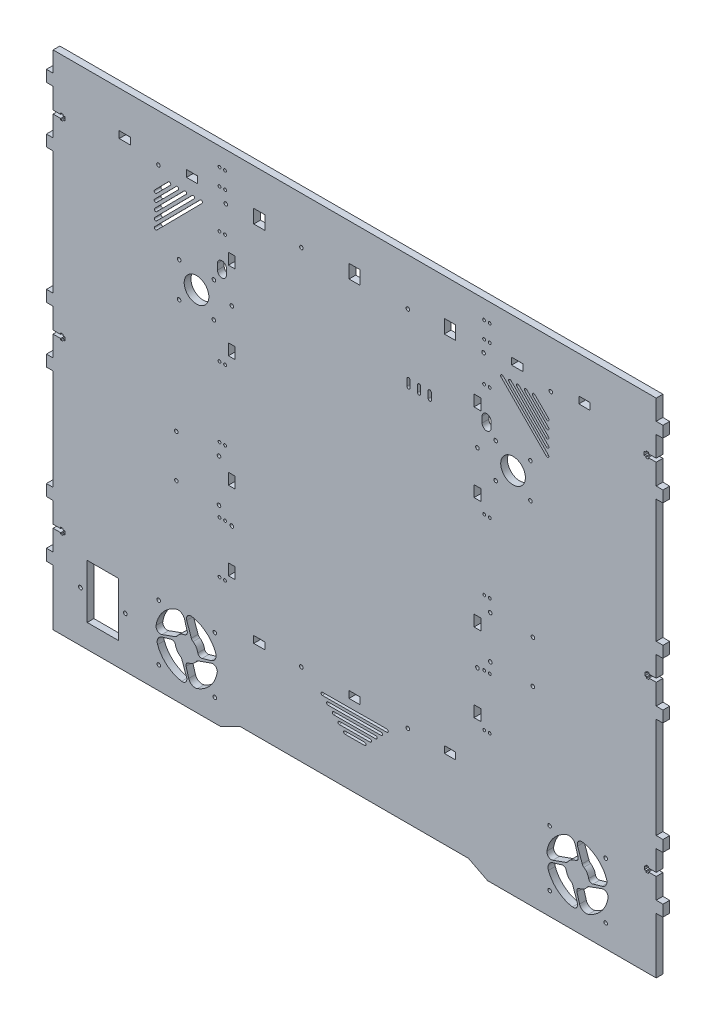
SolidWorks part; units mm, degrees
material "Клен"
ref_plane "Front" through (0, 0, 0) normal (0, 0, 1) x (1, 0, 0)
ref_plane "Top" through (0, 0, 0) normal (0, 1, 0) x (1, 0, 0)
ref_plane "Right" through (0, 0, 0) normal (1, 0, 0) x (0, 0, -1)
sketch "Эскиз1" plane through (0, 0, 0) normal (0, 0, 1) x (1, 0, 0)
  line L3 (1048.7554, 42.0072) -> (1198.2753, 42.0072)
  line L6 (1048.7554, 490.0072) -> (1586.0184, 490.0072)
  line L12 (1586.7554, 42.6812) -> (1586.7554, 42.0072)
  line L13 (1397.7554, 445.0072) -> (1407.7554, 445.0072)
  line L14 (1407.7554, 445.0072) -> (1407.7554, 457.1072)
  line L15 (1407.7554, 457.1072) -> (1397.7554, 457.1072)
  line L16 (1397.7554, 457.1072) -> (1397.7554, 445.0072)
  line L17 (1048.7554, 42.6769) -> (1048.7554, 42.0072)
  line L21 (1227.7554, 445.0072) -> (1237.7554, 445.0072)
  line L22 (1237.7554, 445.0072) -> (1237.7554, 457.1072)
  line L23 (1237.7554, 457.1072) -> (1227.7554, 457.1072)
  line L24 (1227.7554, 457.1072) -> (1227.7554, 445.0072)
  line L25 (1312.7554, 445.0072) -> (1322.7554, 445.0072)
  line L26 (1322.7554, 445.0072) -> (1322.7554, 457.1072)
  line L27 (1322.7554, 457.1072) -> (1312.7554, 457.1072)
  line L28 (1312.7554, 457.1072) -> (1312.7554, 445.0072)
  line L48 (1167.7554, 451.0072) -> (1177.7554, 451.0072)
  line L49 (1177.7554, 451.0072) -> (1177.7554, 457.1072)
  line L50 (1177.7554, 457.1072) -> (1167.7554, 457.1072)
  line L51 (1167.7554, 457.1072) -> (1167.7554, 451.0072)
  line L56 (1457.7554, 451.0072) -> (1467.7554, 451.0072)
  line L57 (1467.7554, 451.0072) -> (1467.7554, 457.1072)
  line L58 (1467.7554, 457.1072) -> (1457.7554, 457.1072)
  line L59 (1457.7554, 457.1072) -> (1457.7554, 451.0072)
  line L92 (1397.7554, 121.0049) -> (1407.7554, 121.0049)
  line L93 (1407.7554, 121.0049) -> (1407.7554, 127.1049)
  line L94 (1407.7554, 127.1049) -> (1397.7554, 127.1049)
  line L95 (1397.7554, 127.1049) -> (1397.7554, 121.0049)
  line L96 (1312.7554, 121.0049) -> (1322.7554, 121.0049)
  line L97 (1322.7554, 121.0049) -> (1322.7554, 127.1049)
  line L98 (1322.7554, 127.1049) -> (1312.7554, 127.1049)
  line L99 (1312.7554, 127.1049) -> (1312.7554, 121.0049)
  line L100 (1227.7554, 121.0049) -> (1237.7554, 121.0049)
  line L101 (1237.7554, 121.0049) -> (1237.7554, 127.1049)
  line L102 (1237.7554, 127.1049) -> (1227.7554, 127.1049)
  line L143 (1227.7554, 127.1049) -> (1227.7554, 121.0049)
  line L148 (1079.1628, 110.8776) -> (1079.1628, 62.8776)
  line L154 (1455.45, 437.0308) -> (1488.8515, 403.2582)
  line L159 (1107.1628, 110.8776) -> (1079.1628, 110.8776)
  line L160 (1079.1628, 62.8776) -> (1107.1628, 62.8776)
  line L161 (1107.1628, 62.8776) -> (1107.1628, 110.8776)
  line L172 (1326.6292, 91.6177) -> (1309.1294, 91.521)
  line L173 (1309.1156, 94.021) -> (1326.6154, 94.1176)
  line L174 (1331.6015, 96.6452) -> (1304.1019, 96.4933)
  line L175 (1304.0881, 98.9933) -> (1331.5877, 99.1452)
  line L176 (1336.5738, 101.6728) -> (1299.0744, 101.4656)
  line L177 (1299.0605, 103.9656) -> (1336.56, 104.1727)
  line L178 (1289.0054, 113.9102) -> (1346.5046, 114.2278)
  line L179 (1346.5184, 111.7279) -> (1289.0193, 111.4102)
  line L180 (1341.5461, 106.7003) -> (1294.0468, 106.4379)
  line L181 (1294.033, 108.9379) -> (1341.5323, 109.2003)
  line L182 (1490.629, 405.0162) -> (1457.2275, 438.7888)
  line L183 (1448.379, 437.0699) -> (1488.8124, 396.1873)
  line L184 (1469.5919, 436.9527) -> (1488.9296, 417.4001)
  line L185 (1476.6629, 436.9136) -> (1488.9687, 424.4711)
  line L186 (1490.5899, 397.9452) -> (1450.1565, 438.8279)
  line L187 (1490.7071, 419.1581) -> (1471.3694, 438.7107)
  line L188 (1462.521, 436.9918) -> (1488.8906, 410.3292)
  line L189 (1490.7462, 426.2291) -> (1478.4404, 438.6716)
  line L198 (1530.3174, 86.3769) -> (1538.4752, 88.7337)
  line L199 (1494.5571, 86.9094) -> (1506.2002, 91.0661)
  line L200 (1517.0418, 100.6255) -> (1514.685, 108.7833)
  line L201 (1502.7664, 87.3542) -> (1494.6086, 84.9974)
  line L202 (1538.538, 86.8062) -> (1526.8948, 82.6495)
  line L203 (1516.0532, 73.09) -> (1518.4101, 64.9322)
  line L204 (1516.4826, 64.8695) -> (1512.3258, 76.5127)
  line L205 (1516.6012, 108.8616) -> (1520.758, 97.2184)
  line L210 (1215.2753, 50.7072) -> (1198.2753, 42.0072)
  line L268 (1215.2753, 50.7072) -> (1419.2753, 50.7072)
  line L269 (1419.2753, 50.7072) -> (1436.2753, 42.0072)
  line L270 (1436.2753, 42.0072) -> (1586.7554, 42.0072)
  line L271 (1490.6681, 412.0872) -> (1464.2985, 438.7498)
  line L272 (1181.6577, 437.9061) -> (1141.2243, 397.0234)
  line L273 (1139.4468, 398.7814) -> (1179.8802, 439.6641)
  line L274 (1139.2905, 427.0652) -> (1151.5963, 439.5078)
  line L275 (1174.5867, 437.867) -> (1141.1852, 404.0944)
  line L276 (1153.3738, 437.7498) -> (1141.068, 425.3073)
  line L277 (1139.3296, 419.9943) -> (1158.6673, 439.5469)
  line L278 (1160.4448, 437.7889) -> (1141.1071, 418.2363)
  line L279 (1167.5157, 437.8279) -> (1141.1461, 411.1653)
  line L280 (1139.3686, 412.9233) -> (1165.7382, 439.5859)
  line L301 (1139.4077, 405.8524) -> (1172.8092, 439.625)
  line L302 (1527.7554, 457.1072) -> (1517.7554, 457.1072)
  line L303 (1517.7554, 451.0072) -> (1527.7554, 451.0072)
  line L304 (1517.7554, 457.1072) -> (1517.7554, 451.0072)
  line L305 (1527.7554, 451.0072) -> (1527.7554, 457.1072)
  line L306 (1117.7554, 451.0072) -> (1117.7554, 457.1072)
  line L307 (1107.7554, 457.1072) -> (1107.7554, 451.0072)
  line L308 (1117.7554, 457.1072) -> (1107.7554, 457.1072)
  line L309 (1107.7554, 451.0072) -> (1117.7554, 451.0072)
  line L310 (1167.825, 64.8695) -> (1163.6683, 76.5127)
  line L348 (1592.7554, 462.0158) -> (1586.7554, 461.9158)
  line L358 (1059.2554, 440.4572) -> (1059.2554, 443.5572)
  line L359 (1057.7554, 439.2572) -> (1057.7554, 440.4572)
  line L360 (1048.7554, 477.0072) -> (1048.7554, 490.0072)
  line L361 (1057.7554, 270.4572) -> (1059.2554, 270.4572)
  line L362 (1055.5554, 270.4572) -> (1055.5554, 269.2572)
  line L363 (1430.3554, 401.9072) -> (1430.3554, 411.9072)
  line L364 (1430.3554, 411.9072) -> (1424.2554, 411.9072)
  line L365 (1424.2554, 411.9072) -> (1424.2554, 401.9072)
  line L366 (1424.2554, 401.9072) -> (1430.3554, 401.9072)
  line L367 (1430.3554, 331.9072) -> (1430.3554, 341.9072)
  line L368 (1430.3554, 341.9072) -> (1424.2554, 341.9072)
  line L369 (1424.2554, 341.9072) -> (1424.2554, 331.9072)
  line L370 (1424.2554, 331.9072) -> (1430.3554, 331.9072)
  line L371 (1430.3554, 231.9072) -> (1430.3554, 241.9072)
  line L372 (1430.3554, 241.9072) -> (1424.2554, 241.9072)
  line L373 (1424.2554, 241.9072) -> (1424.2554, 231.9072)
  line L374 (1424.2554, 231.9072) -> (1430.3554, 231.9072)
  line L375 (1424.2554, 171.9072) -> (1424.2554, 161.9072)
  line L376 (1424.2554, 161.9072) -> (1430.3554, 161.9072)
  line L377 (1430.3554, 161.9072) -> (1430.3554, 171.9072)
  line L378 (1430.3554, 171.9072) -> (1424.2554, 171.9072)
  line L379 (1205.1554, 161.9072) -> (1211.2554, 161.9072)
  line L380 (1211.2554, 161.9072) -> (1211.2554, 171.9072)
  line L381 (1205.1554, 171.9072) -> (1205.1554, 161.9072)
  line L382 (1211.2554, 171.9072) -> (1205.1554, 171.9072)
  line L383 (1211.2554, 231.9072) -> (1211.2554, 241.9072)
  line L384 (1211.2554, 241.9072) -> (1205.1554, 241.9072)
  line L385 (1205.1554, 241.9072) -> (1205.1554, 231.9072)
  line L386 (1205.1554, 231.9072) -> (1211.2554, 231.9072)
  line L387 (1205.1554, 331.9072) -> (1211.2554, 331.9072)
  line L388 (1211.2554, 331.9072) -> (1211.2554, 341.9072)
  line L389 (1205.1554, 341.9072) -> (1205.1554, 331.9072)
  line L390 (1211.2554, 341.9072) -> (1205.1554, 341.9072)
  line L391 (1205.1554, 401.9072) -> (1211.2554, 401.9072)
  line L392 (1211.2554, 401.9072) -> (1211.2554, 411.9072)
  line L393 (1211.2554, 411.9072) -> (1205.1554, 411.9072)
  line L394 (1205.1554, 411.9072) -> (1205.1554, 401.9072)
  line L395 (1145.8995, 86.9094) -> (1157.5427, 91.0661)
  line L396 (1189.8804, 86.8062) -> (1178.2373, 82.6495)
  line L397 (1167.3957, 73.09) -> (1169.7525, 64.9322)
  line L398 (1154.1089, 87.3542) -> (1145.951, 84.9974)
  line L399 (1181.6599, 86.3769) -> (1189.8177, 88.7337)
  line L400 (1167.9437, 108.8616) -> (1172.1004, 97.2184)
  line L414 (1057.7554, 119.2572) -> (1057.7554, 120.4572)
  line L415 (1168.3843, 100.6255) -> (1166.0274, 108.7833)
  line L416 (1317.7554, 12.4246) -> (1317.7554, 537.1765) construction
  line L417 (1586.7554, 537.1765) -> (1586.7554, 12.4246) construction
  line L418 (1048.7554, 537.1765) -> (1048.7554, -11.6164) construction
  line L419 (1042.7554, 92.0072) -> (1042.7554, 102.0072)
  line L420 (1431.4302, 398.3485) -> (1431.4302, 393.0655)
  line L421 (1439.4302, 393.0655) -> (1439.4302, 398.3485)
  line L422 (1048.7554, 123.5572) -> (1048.7554, 141.9072)
  line L423 (1048.7554, 472.1072) -> (1048.7554, 477.0072)
  line L424 (1195.3774, 398.4163) -> (1195.3774, 393.1334)
  line L425 (1203.3774, 393.1334) -> (1203.3774, 398.4163)
  line L426 (1059.2554, 123.5572) -> (1057.7554, 123.5572)
  line L427 (1057.7554, 274.7572) -> (1055.5554, 274.7572)
  line L428 (1383.3554, 394.0072) -> (1383.3554, 388.0072)
  line L429 (1386.1554, 388.0072) -> (1386.1554, 394.0072)
  line L430 (1042.7554, 102.0072) -> (1048.7554, 102.1072)
  line L431 (1057.7554, 120.4572) -> (1059.2554, 120.4572)
  line L432 (1373.8554, 394.0072) -> (1373.8554, 388.0072)
  line L433 (1376.6554, 388.0072) -> (1376.6554, 394.0072)
  line L434 (1042.7554, 142.0072) -> (1042.7554, 152.0072)
  line L435 (1042.7554, 302.0072) -> (1048.7554, 302.1072)
  line L436 (1364.3554, 394.0072) -> (1364.3554, 388.0072)
  line L437 (1367.1554, 388.0072) -> (1367.1554, 394.0072)
  line L438 (1055.5554, 120.4572) -> (1055.5554, 119.2572)
  line L439 (1048.7554, 411.9072) -> (1042.7554, 412.0072)
  line L440 (1055.5554, 444.7572) -> (1055.5554, 443.5572)
  line L441 (1057.7554, 124.7572) -> (1055.5554, 124.7572)
  line L442 (1055.5554, 443.5572) -> (1048.7554, 443.5572)
  line L443 (1048.7554, 120.4572) -> (1055.5554, 120.4572)
  line L444 (1042.7554, 242.0072) -> (1042.7554, 252.0072)
  line L445 (1055.5554, 269.2572) -> (1057.7554, 269.2572)
  line L446 (1055.5554, 274.7572) -> (1055.5554, 273.5572)
  line L447 (1048.7554, 461.9072) -> (1042.7554, 462.0072)
  line L448 (1048.7554, 102.1072) -> (1048.7554, 120.4572)
  line L449 (1057.7554, 440.4572) -> (1059.2554, 440.4572)
  line L450 (1048.7554, 252.1072) -> (1048.7554, 270.4572)
  line L451 (1042.7554, 292.0072) -> (1042.7554, 302.0072)
  line L452 (1042.7554, 472.0072) -> (1048.7554, 472.1072)
  line L453 (1059.2554, 443.5572) -> (1057.7554, 443.5572)
  line L454 (1048.7554, 42.6769) -> (1048.7554, 91.9072)
  line L455 (1048.7554, 273.5572) -> (1048.7554, 291.9072)
  line L456 (1055.5554, 440.4572) -> (1055.5554, 439.2572)
  line L457 (1055.5554, 439.2572) -> (1057.7554, 439.2572)
  line L458 (1042.7554, 422.0072) -> (1048.7554, 422.1072)
  line L459 (1048.7554, 443.5572) -> (1048.7554, 461.9072)
  line L460 (1048.7554, 141.9072) -> (1042.7554, 142.0072)
  line L461 (1048.7554, 302.1072) -> (1048.7554, 411.9072)
  line L462 (1048.7554, 91.9072) -> (1042.7554, 92.0072)
  line L463 (1048.7554, 270.4572) -> (1055.5554, 270.4572)
  line L464 (1048.7554, 291.9072) -> (1042.7554, 292.0072)
  line L465 (1059.2554, 120.4572) -> (1059.2554, 123.5572)
  line L466 (1057.7554, 273.5572) -> (1057.7554, 274.7572)
  line L467 (1042.7554, 252.0072) -> (1048.7554, 252.1072)
  line L468 (1059.2554, 273.5572) -> (1057.7554, 273.5572)
  line L469 (1048.7554, 422.1072) -> (1048.7554, 440.4572)
  line L470 (1042.7554, 462.0072) -> (1042.7554, 472.0072)
  line L471 (1057.7554, 269.2572) -> (1057.7554, 270.4572)
  line L472 (1057.7554, 443.5572) -> (1057.7554, 444.7572)
  line L473 (1042.7554, 152.0072) -> (1048.7554, 152.1072)
  line L474 (1059.2554, 270.4572) -> (1059.2554, 273.5572)
  line L475 (1055.5554, 273.5572) -> (1048.7554, 273.5572)
  line L476 (1048.7554, 152.1072) -> (1048.7554, 241.9072)
  line L477 (1057.7554, 444.7572) -> (1055.5554, 444.7572)
  line L478 (1055.5554, 124.7572) -> (1055.5554, 123.5572)
  line L479 (1048.7554, 241.9072) -> (1042.7554, 242.0072)
  line L480 (1055.5554, 123.5572) -> (1048.7554, 123.5572)
  line L481 (1057.7554, 123.5572) -> (1057.7554, 124.7572)
  line L482 (1055.5554, 119.2572) -> (1057.7554, 119.2572)
  line L483 (1042.7554, 412.0072) -> (1042.7554, 422.0072)
  line L484 (1048.7554, 440.4572) -> (1055.5554, 440.4572)
  line L487 (1586.0184, 490.0072) -> (1586.7554, 490.0072)
  line L488 (1586.7554, 302.1072) -> (1592.7554, 302.0072)
  line L489 (1592.7554, 252.0072) -> (1592.7554, 242.0072)
  line L490 (1579.6985, 444.7615) -> (1577.4985, 444.7615)
  line L491 (1592.7554, 472.0072) -> (1592.7554, 462.0158)
  line L492 (1579.9554, 120.4572) -> (1586.7554, 120.4572)
  line L493 (1592.7554, 102.0072) -> (1592.7554, 92.0072)
  line L494 (1579.9554, 123.5572) -> (1579.9554, 124.7572)
  line L495 (1586.7554, 490.0072) -> (1586.7554, 472.1072)
  line L496 (1577.7554, 120.4572) -> (1577.7554, 119.2572)
  line L497 (1578.2356, 269.2572) -> (1580.4356, 269.2572)
  line L498 (1575.9985, 440.4615) -> (1577.4985, 440.4615)
  line L499 (1580.4356, 274.7572) -> (1578.2356, 274.7572)
  line L500 (1577.7554, 123.5572) -> (1576.2554, 123.5572)
  line L501 (1576.7356, 273.5572) -> (1576.7356, 270.4572)
  line L502 (1586.4985, 443.5615) -> (1586.7554, 443.5615)
  line L503 (1578.2356, 274.7572) -> (1578.2356, 273.5572)
  line L504 (1577.4985, 439.2615) -> (1579.6985, 439.2615)
  line L505 (1576.2554, 120.4572) -> (1577.7554, 120.4572)
  line L506 (1586.4985, 443.5615) -> (1579.6985, 443.5615)
  line L507 (1586.7554, 141.9072) -> (1586.7554, 123.5572)
  line L508 (1592.7554, 142.0072) -> (1586.7554, 141.9072)
  line L509 (1586.7554, 252.1072) -> (1592.7554, 252.0072)
  line L510 (1578.2356, 270.4572) -> (1578.2356, 269.2572)
  line L511 (1580.4356, 270.4572) -> (1586.7554, 270.4572)
  line L512 (1579.9554, 124.7572) -> (1577.7554, 124.7572)
  line L513 (1577.7554, 124.7572) -> (1577.7554, 123.5572)
  line L514 (1592.7554, 142.0072) -> (1592.7554, 152.0072)
  line L515 (1579.6985, 440.4615) -> (1586.4985, 440.4615)
  line L516 (1592.7554, 412.0072) -> (1586.7554, 411.9072)
  line L517 (1580.4356, 269.2572) -> (1580.4356, 270.4572)
  line L518 (1586.7554, 91.9072) -> (1586.7554, 42.6812)
  line L519 (1592.7554, 242.0072) -> (1586.7554, 241.9072)
  line L520 (1579.6985, 439.2615) -> (1579.6985, 440.4615)
  line L521 (1580.4356, 273.5572) -> (1580.4356, 274.7572)
  line L522 (1586.7554, 270.4572) -> (1586.7554, 252.1072)
  line L523 (1577.4985, 443.5615) -> (1575.9985, 443.5615)
  line L524 (1586.7554, 152.1072) -> (1592.7554, 152.0072)
  line L525 (1577.7554, 119.2572) -> (1579.9554, 119.2572)
  line L526 (1592.7554, 422.0072) -> (1592.7554, 412.0072)
  line L527 (1586.7554, 422.1072) -> (1592.7554, 422.0072)
  line L528 (1579.9554, 119.2572) -> (1579.9554, 120.4572)
  line L529 (1586.7554, 273.5572) -> (1580.4356, 273.5572)
  line L530 (1586.7554, 123.5572) -> (1579.9554, 123.5572)
  line L531 (1586.4985, 440.4615) -> (1586.7554, 440.4615)
  line L532 (1576.7356, 270.4572) -> (1578.2356, 270.4572)
  line L533 (1586.7554, 461.9158) -> (1586.7554, 443.5615)
  line L534 (1575.9985, 443.5615) -> (1575.9985, 440.4615)
  line L535 (1592.7554, 292.0072) -> (1586.7554, 291.9072)
  line L536 (1586.7554, 120.4572) -> (1586.7554, 102.1072)
  line L537 (1576.2554, 123.5572) -> (1576.2554, 120.4572)
  line L538 (1586.7554, 102.1072) -> (1592.7554, 102.0072)
  line L539 (1592.7554, 92.0072) -> (1586.7554, 91.9072)
  line L540 (1586.7554, 411.9072) -> (1586.7554, 302.1072)
  line L541 (1592.7554, 302.0072) -> (1592.7554, 292.0072)
  line L542 (1577.4985, 444.7615) -> (1577.4985, 443.5615)
  line L543 (1579.6985, 443.5615) -> (1579.6985, 444.7615)
  line L544 (1586.7554, 241.9072) -> (1586.7554, 152.1072)
  line L545 (1586.7554, 440.4615) -> (1586.7554, 422.1072)
  line L546 (1586.7554, 291.9072) -> (1586.7554, 273.5572)
  line L547 (1578.2356, 273.5572) -> (1576.7356, 273.5572)
  line L548 (1586.7554, 472.1072) -> (1592.7554, 472.0072)
  line L549 (1577.4985, 440.4615) -> (1577.4985, 439.2615)
  circle A4 centre (1202.7554, 448.0572) radius 1.6
  circle A5 centre (1432.7554, 448.0572) radius 1.6
  circle A6 centre (1365.2554, 448.0572) radius 1.6
  circle A7 centre (1270.2554, 448.0572) radius 1.6
  circle A14 centre (1365.2554, 124.0549) radius 1.6
  circle A15 centre (1270.2554, 124.0549) radius 1.6
  circle A20 centre (1492.7554, 448.0572) radius 1.6
  circle A21 centre (1142.7554, 448.0572) radius 1.6
  circle A24 centre (1073.1628, 86.8776) radius 1.65
  circle A25 centre (1113.1628, 86.8776) radius 1.65
  arc A36 (1326.6292, 91.6177) -> (1326.6154, 94.1176) centre (1326.6223, 92.8677) ccw
  arc A37 (1309.1156, 94.021) -> (1309.1294, 91.521) centre (1309.1225, 92.771) ccw
  arc A38 (1304.0881, 98.9933) -> (1304.1019, 96.4933) centre (1304.095, 97.7433) ccw
  arc A39 (1331.6015, 96.6452) -> (1331.5877, 99.1452) centre (1331.5946, 97.8952) ccw
  arc A40 (1336.5738, 101.6728) -> (1336.56, 104.1727) centre (1336.5669, 102.9228) ccw
  arc A41 (1299.0605, 103.9656) -> (1299.0744, 101.4656) centre (1299.0674, 102.7156) ccw
  arc A42 (1294.033, 108.9379) -> (1294.0468, 106.4379) centre (1294.0399, 107.6879) ccw
  arc A43 (1341.5461, 106.7003) -> (1341.5323, 109.2003) centre (1341.5392, 107.9503) ccw
  arc A44 (1346.5184, 111.7279) -> (1346.5046, 114.2278) centre (1346.5115, 112.9779) ccw
  arc A45 (1289.0054, 113.9102) -> (1289.0193, 111.4102) centre (1289.0124, 112.6602) ccw
  arc A46 (1157.5427, 91.0661) -> (1159.5017, 92.5785) centre (1156.1978, 94.8332) ccw
  arc A47 (1450.1565, 438.8279) -> (1448.379, 437.0699) centre (1449.2678, 437.9489) ccw
  arc A48 (1471.3694, 438.7107) -> (1469.5919, 436.9527) centre (1470.4807, 437.8317) ccw
  arc A49 (1457.2275, 438.7888) -> (1455.45, 437.0308) centre (1456.3388, 437.9098) ccw
  arc A50 (1488.9687, 424.4711) -> (1490.7462, 426.2291) centre (1489.8574, 425.3501) ccw
  arc A51 (1488.8515, 403.2582) -> (1490.629, 405.0162) centre (1489.7403, 404.1372) ccw
  arc A52 (1488.8124, 396.1873) -> (1490.5899, 397.9452) centre (1489.7012, 397.0662) ccw
  arc A53 (1488.8906, 410.3292) -> (1490.6681, 412.0872) centre (1489.7793, 411.2082) ccw
  arc A54 (1488.9296, 417.4001) -> (1490.7071, 419.1581) centre (1489.8184, 418.2791) ccw
  arc A55 (1478.4404, 438.6716) -> (1476.6629, 436.9136) centre (1477.5516, 437.7926) ccw
  arc A56 (1464.2985, 438.7498) -> (1462.521, 436.9918) centre (1463.4097, 437.8708) ccw
  arc A57 (1139.3296, 419.9943) -> (1141.1071, 418.2363) centre (1140.2183, 419.1153) ccw
  arc A58 (1174.5867, 437.867) -> (1172.8092, 439.625) centre (1173.698, 438.746) ccw
  arc A59 (1167.5157, 437.8279) -> (1165.7382, 439.5859) centre (1166.627, 438.7069) ccw
  arc A60 (1139.4468, 398.7814) -> (1141.2243, 397.0234) centre (1140.3355, 397.9024) ccw
  arc A61 (1153.3738, 437.7498) -> (1151.5963, 439.5078) centre (1152.4851, 438.6288) ccw
  arc A62 (1139.3686, 412.9233) -> (1141.1461, 411.1653) centre (1140.2574, 412.0443) ccw
  arc A63 (1160.4448, 437.7889) -> (1158.6673, 439.5469) centre (1159.556, 438.6679) ccw
  arc A64 (1181.6577, 437.9061) -> (1179.8802, 439.6641) centre (1180.7689, 438.7851) ccw
  arc A65 (1139.2905, 427.0652) -> (1141.068, 425.3073) centre (1140.1793, 426.1863) ccw
  arc A66 (1139.4077, 405.8524) -> (1141.1852, 404.0944) centre (1140.2965, 404.9734) ccw
  arc A67 (1166.0274, 108.7833) -> (1158.15, 112.7336) centre (1160.2632, 107.118) ccw
  arc A68 (1189.8177, 88.7337) -> (1193.7679, 96.6112) centre (1188.1523, 94.498) ccw
  circle A69 centre (1143.0318, 112.013) radius 1.6
  circle A70 centre (1143.0318, 62.013) radius 1.6
  arc A71 (1166.0477, 96.8429) -> (1168.3843, 100.6255) centre (1165.5021, 99.7929) ccw
  arc A72 (1145.951, 84.9974) -> (1142.0008, 77.1199) centre (1147.6164, 79.2331) ccw
  arc A100 (1178.2373, 82.6495) -> (1176.2782, 81.1371) centre (1179.5822, 78.8823) ccw
  arc A102 (1538.4752, 88.7337) -> (1542.4254, 96.6112) centre (1536.8099, 94.498) ccw
  arc A103 (1526.2875, 60.982) -> (1543.8306, 82.3942) centre (1516.5531, 86.85) ccw
  arc A104 (1512.3258, 76.5127) -> (1510.8135, 78.4717) centre (1508.5587, 75.1677) ccw
  arc A105 (1518.3898, 76.8727) -> (1516.0532, 73.09) centre (1518.9354, 73.9227) ccw
  arc A106 (1489.2645, 91.3213) -> (1494.5571, 86.9094) centre (1493.2122, 90.6765) ccw
  arc A107 (1512.0706, 59.5769) -> (1516.4826, 64.8695) centre (1512.7155, 63.5246) ccw
  arc A108 (1506.2002, 91.0661) -> (1508.1593, 92.5785) centre (1504.8553, 94.8332) ccw
  arc A109 (1521.0132, 114.1542) -> (1516.6012, 108.8616) centre (1520.3684, 110.2065) ccw
  arc A110 (1518.3898, 76.8727) -> (1524.9358, 81.1371) centre (1516.5419, 86.8655) ccw
  circle A111 centre (1541.6893, 112.013) radius 1.6
  arc A112 (1494.6086, 84.9974) -> (1490.6584, 77.1199) centre (1496.2739, 79.2331) ccw
  arc A113 (1506.5491, 85.0176) -> (1510.8135, 78.4717) centre (1516.5419, 86.8655) ccw
  arc A114 (1526.8948, 82.6495) -> (1524.9358, 81.1371) centre (1528.2397, 78.8823) ccw
  circle A115 centre (1541.6893, 62.013) radius 1.6
  arc A116 (1490.6584, 77.1199) -> (1512.0706, 59.5769) centre (1516.5264, 86.8543) ccw
  arc A117 (1514.685, 108.7833) -> (1506.8075, 112.7336) centre (1508.9207, 107.118) ccw
  circle A118 centre (1491.6893, 112.013) radius 1.6
  arc A119 (1520.758, 97.2184) -> (1522.2703, 95.2594) centre (1524.5251, 98.5634) ccw
  arc A120 (1542.4254, 96.6112) -> (1521.0132, 114.1542) centre (1516.5574, 86.8768) ccw
  arc A121 (1526.5348, 88.7135) -> (1522.2703, 95.2594) centre (1516.5419, 86.8655) ccw
  arc A122 (1506.8075, 112.7336) -> (1489.2645, 91.3213) centre (1516.5419, 86.8655) ccw
  arc A123 (1506.5491, 85.0176) -> (1502.7664, 87.3542) centre (1503.5991, 84.4721) ccw
  arc A124 (1514.7052, 96.8429) -> (1508.1593, 92.5785) centre (1516.5531, 86.85) ccw
  arc A125 (1543.8306, 82.3942) -> (1538.538, 86.8062) centre (1539.8829, 83.0391) ccw
  circle A126 centre (1491.6893, 62.013) radius 1.6
  arc A127 (1518.4101, 64.9322) -> (1526.2875, 60.982) centre (1524.1743, 66.5976) ccw
  arc A128 (1526.5348, 88.7135) -> (1530.3174, 86.3769) centre (1529.4848, 89.259) ccw
  arc A129 (1514.7052, 96.8429) -> (1517.0418, 100.6255) centre (1514.1597, 99.7929) ccw
  arc A130 (1157.8915, 85.0176) -> (1154.1089, 87.3542) centre (1154.9415, 84.4721) ccw
  arc A131 (1172.3557, 114.1542) -> (1167.9437, 108.8616) centre (1171.7108, 110.2065) ccw
  arc A132 (1172.1004, 97.2184) -> (1173.6128, 95.2594) centre (1175.8676, 98.5634) ccw
  arc A133 (1177.63, 60.982) -> (1195.173, 82.3942) centre (1167.8956, 86.85) ccw
  arc A134 (1193.7679, 96.6112) -> (1172.3557, 114.1542) centre (1167.8999, 86.8768) ccw
  circle A135 centre (1193.0318, 62.013) radius 1.6
  arc A136 (1166.0477, 96.8429) -> (1159.5017, 92.5785) centre (1167.8956, 86.85) ccw
  arc A137 (1169.7525, 64.9322) -> (1177.63, 60.982) centre (1175.5168, 66.5976) ccw
  arc A138 (1169.7323, 76.8727) -> (1176.2782, 81.1371) centre (1167.8844, 86.8655) ccw
  arc A139 (1177.8772, 88.7135) -> (1173.6128, 95.2594) centre (1167.8844, 86.8655) ccw
  arc A160 (1169.7323, 76.8727) -> (1167.3957, 73.09) centre (1170.2778, 73.9227) ccw
  arc A161 (1157.8915, 85.0176) -> (1162.1559, 78.4717) centre (1167.8844, 86.8655) ccw
  arc A162 (1163.4131, 59.5769) -> (1167.825, 64.8695) centre (1164.0579, 63.5246) ccw
  arc A163 (1142.0008, 77.1199) -> (1163.4131, 59.5769) centre (1167.8688, 86.8543) ccw
  arc A164 (1163.6683, 76.5127) -> (1162.1559, 78.4717) centre (1159.9012, 75.1677) ccw
  arc A165 (1195.173, 82.3942) -> (1189.8804, 86.8062) centre (1191.2253, 83.0391) ccw
  arc A166 (1177.8772, 88.7135) -> (1181.6599, 86.3769) centre (1180.8272, 89.259) ccw
  circle A167 centre (1193.0318, 112.013) radius 1.6
  arc A168 (1158.15, 112.7336) -> (1140.6069, 91.3213) centre (1167.8844, 86.8655) ccw
  arc A169 (1140.6069, 91.3213) -> (1145.8995, 86.9094) centre (1144.5546, 90.6765) ccw
  circle A194 centre (1427.3054, 371.9072) radius 1.6
  circle A195 centre (1427.3054, 201.9072) radius 1.6
  circle A196 centre (1208.2054, 201.9072) radius 1.6
  circle A197 centre (1208.2054, 371.9072) radius 1.6
  circle A220 centre (1202.1959, 261.1916) radius 1.25
  circle A221 centre (1197.2245, 261.2595) radius 1.25
  circle A222 centre (1196.7541, 250.2739) radius 1.6
  circle A223 centre (1158.7541, 250.2739) radius 1.6
  circle A224 centre (1158.7541, 212.2739) radius 1.6
  circle A225 centre (1196.7541, 212.2739) radius 1.6
  circle A226 centre (1202.1604, 202.9749) radius 1.25
  circle A227 centre (1197.189, 203.0428) radius 1.25
  circle A228 centre (1202.1586, 156.838) radius 1.25
  circle A229 centre (1197.1872, 156.9059) radius 1.25
  circle A232 centre (1438.3088, 156.7702) radius 1.25
  circle A234 centre (1433.3374, 156.838) radius 1.25
  circle A236 centre (1433.3392, 202.9749) radius 1.25
  circle A238 centre (1438.7554, 212.2739) radius 1.6
  circle A240 centre (1438.3106, 202.907) radius 1.25
  circle A242 centre (1476.7554, 212.2739) radius 1.6
  circle A244 centre (1476.7554, 250.2739) radius 1.6
  circle A246 centre (1438.7554, 250.2739) radius 1.6
  circle A248 centre (1438.3461, 261.1238) radius 1.25
  circle A250 centre (1433.3748, 261.1916) radius 1.25
  circle A252 centre (1438.3268, 323.4135) radius 1.25
  circle A254 centre (1433.3554, 323.4814) radius 1.25
  arc A258 (1431.4302, 393.0655) -> (1439.4302, 393.0655) centre (1435.4302, 393.0655) ccw
  arc A259 (1439.4302, 398.3485) -> (1431.4302, 398.3485) centre (1435.4302, 398.3485) ccw
  circle A260 centre (1443.5699, 354.6399) radius 1.6
  circle A262 centre (1474.5699, 354.6399) radius 1.6
  circle A264 centre (1474.5699, 385.6399) radius 1.6
  circle A266 centre (1443.5699, 385.6399) radius 1.6
  circle A268 centre (1438.1921, 423.9311) radius 1.25
  circle A270 centre (1433.2207, 423.999) radius 1.25
  circle A272 centre (1438.2083, 473.5059) radius 1.25
  circle A274 centre (1433.2369, 473.5737) radius 1.25
  circle A276 centre (1438.2276, 458.6064) radius 1.25
  circle A278 centre (1433.2562, 458.6743) radius 1.25
  circle A280 centre (1202.1766, 323.4814) radius 1.25
  circle A282 centre (1197.2052, 323.5492) radius 1.25
  circle A284 centre (1161.2104, 384.1399) radius 1.6
  circle A286 centre (1161.2104, 353.1399) radius 1.6
  circle A288 centre (1176.7104, 368.6399) radius 11
  circle A290 centre (1192.2104, 353.1399) radius 1.6
  circle A292 centre (1192.2104, 384.1399) radius 1.6
  arc A296 (1195.3774, 393.1334) -> (1203.3774, 393.1334) centre (1199.3774, 393.1334) ccw
  arc A297 (1203.3774, 398.4163) -> (1195.3774, 398.4163) centre (1199.3774, 398.4163) ccw
  circle A298 centre (1197.1679, 424.0668) radius 1.25
  circle A300 centre (1202.1392, 423.999) radius 1.25
  circle A302 centre (1202.1748, 458.6743) radius 1.25
  circle A304 centre (1197.2034, 458.7421) radius 1.25
  circle A306 centre (1202.1554, 473.5737) radius 1.25
  circle A308 centre (1197.1841, 473.6416) radius 1.25
  arc A312 (1383.3554, 388.0072) -> (1386.1554, 388.0072) centre (1384.7554, 388.0072) ccw
  arc A313 (1386.1554, 394.0072) -> (1383.3554, 394.0072) centre (1384.7554, 394.0072) ccw
  arc A316 (1373.8554, 388.0072) -> (1376.6554, 388.0072) centre (1375.2554, 388.0072) ccw
  arc A317 (1376.6554, 394.0072) -> (1373.8554, 394.0072) centre (1375.2554, 394.0072) ccw
  arc A320 (1364.3554, 388.0072) -> (1367.1554, 388.0072) centre (1365.7554, 388.0072) ccw
  arc A321 (1367.1554, 394.0072) -> (1364.3554, 394.0072) centre (1365.7554, 394.0072) ccw
  circle A322 centre (1459.0699, 370.1399) radius 11
  dimension "D3" = 269
  dimension "D2" = 269
  dimension "D1" = 149.5198
  dimension "D7" = 13
extrude "Бобышка-Вытянуть1" add sketch "Эскиз1" against normal blind 6
